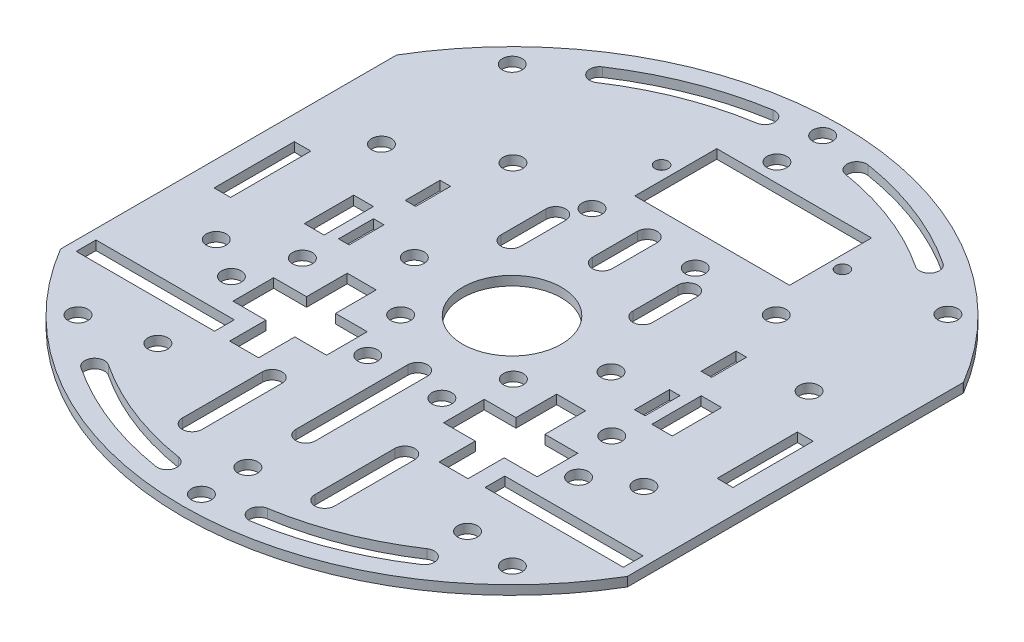
SolidWorks part; units mm, degrees
ref_plane "Plan de face" through (0, 0, 0) normal (0, 0, 1) x (1, 0, 0)
ref_plane "Plan de dessus" through (0, 0, 0) normal (0, 1, 0) x (1, 0, 0)
ref_plane "Plan de droite" through (0, 0, 0) normal (1, 0, 0) x (0, 0, -1)
sketch "Esquisse1" plane through (0, 0, 0) normal (0, 1, 0) x (1, 0, 0)
  line L0 (230, 494) -> (1150, 494) construction
  line L1 (230, 494) -> (1150, 494) construction
  line L2 (1049.7748, 1753.5) -> (2703.7748, 1753.5) construction
  line L3 (35.8344, 116.4831) -> (35.8344, 167.52)
  line L4 (121.9144, 167.4519) -> (121.9144, 116.5513)
  line L5 (88.9323, 158.6153) -> (88.9323, 151.8005) construction
  line L6 (121.9144, 116.5513) -> (121.9144, 116.4831)
  line L7 (55.7773, 128.9032) -> (60.7773, 128.9032)
  line L8 (55.7773, 128.9032) -> (55.7773, 122.7236)
  line L9 (55.7773, 122.7236) -> (60.7773, 122.7236)
  line L10 (60.7773, 122.7236) -> (60.7773, 117.2265)
  line L11 (60.7773, 117.2265) -> (65.1744, 117.2265)
  line L12 (65.1744, 117.2265) -> (65.1744, 122.7236)
  line L13 (65.1744, 122.7236) -> (69.9925, 122.7236)
  line L14 (69.9925, 122.7236) -> (69.9925, 128.9032)
  line L15 (69.9925, 128.9032) -> (65.1744, 128.9032)
  line L16 (65.1744, 128.9032) -> (65.1744, 135.081)
  line L17 (65.1744, 135.081) -> (60.7773, 135.081)
  line L18 (60.7773, 135.081) -> (60.7773, 128.9032)
  line L19 (68.9056, 158.6153) -> (68.9056, 151.8005) construction
  line L20 (70.4056, 158.6153) -> (70.4056, 151.8005)
  line L21 (67.4056, 158.6153) -> (67.4056, 151.8005)
  line L22 (78.7942, 162.6149) -> (78.7942, 155.8001) construction
  line L23 (80.2942, 162.6149) -> (80.2942, 155.8001)
  line L24 (77.2942, 162.6149) -> (77.2942, 155.8001)
  line L25 (68.7987, 115.6611) -> (68.7987, 103.5071) construction
  line L26 (70.2987, 115.6611) -> (70.2987, 103.5071)
  line L27 (67.2987, 115.6611) -> (67.2987, 103.5071)
  line L28 (39.458, 148.3706) -> (41.958, 148.3706)
  line L29 (41.958, 148.3706) -> (41.958, 136.1826)
  line L30 (41.958, 136.1826) -> (39.458, 136.1826)
  line L31 (39.458, 136.1826) -> (39.458, 148.3706)
  line L32 (55.6035, 149.0513) -> (57.2035, 149.0513)
  line L33 (54.0029, 138.3405) -> (51.0029, 138.3405)
  line L34 (54.0029, 138.3405) -> (54.0029, 145.8405)
  line L35 (54.0029, 145.8405) -> (51.0029, 145.8405)
  line L36 (51.0029, 138.3405) -> (51.0029, 145.8405)
  line L37 (55.6035, 138.9387) -> (57.2035, 138.9387)
  line L38 (55.6035, 138.9387) -> (55.6035, 144.2387)
  line L39 (55.6035, 144.2387) -> (57.2035, 144.2387)
  line L40 (57.2035, 138.9387) -> (57.2035, 144.2387)
  line L41 (55.6035, 149.0513) -> (55.6035, 154.3513)
  line L42 (55.6035, 154.3513) -> (57.2035, 154.3513)
  line L43 (57.2035, 149.0513) -> (57.2035, 154.3513)
  line L44 (35.8344, 142.0016) -> (121.9144, 142.0016) construction
  line L45 (78.8744, 142.0016) -> (78.8744, 76.4199) construction
  line L46 (78.9075, 127.6391) -> (78.9075, 110.6391) construction
  line L47 (80.4075, 127.6391) -> (80.4075, 110.6391)
  line L48 (77.4075, 127.6391) -> (77.4075, 110.6391)
  line L49 (35.8344, 162.6149) -> (121.9144, 162.6149) construction
  line L50 (87.4323, 158.6153) -> (87.4323, 151.8005)
  line L51 (90.4323, 158.6153) -> (90.4323, 151.8005)
  line L52 (88.9323, 115.6611) -> (88.9323, 103.5071) construction
  line L53 (87.4323, 115.6611) -> (87.4323, 103.5071)
  line L54 (90.4323, 115.6611) -> (90.4323, 103.5071)
  line L55 (100.5453, 149.0513) -> (100.5453, 154.3513)
  line L56 (102.1454, 154.3551) -> (100.5453, 154.3513)
  line L57 (102.1454, 149.0551) -> (102.1454, 154.3551)
  line L58 (100.5454, 138.9387) -> (100.5454, 144.2387)
  line L59 (102.1454, 144.2387) -> (100.5454, 144.2387)
  line L60 (102.1454, 138.9387) -> (102.1454, 144.2387)
  line L61 (102.1454, 138.9387) -> (100.5454, 138.9387)
  line L62 (106.8661, 138.3405) -> (106.8661, 145.8405)
  line L63 (103.7673, 145.8405) -> (106.8661, 145.8405)
  line L64 (103.7673, 138.3405) -> (103.7673, 145.8405)
  line L65 (103.7673, 138.3405) -> (106.8661, 138.3405)
  line L66 (102.1454, 149.0551) -> (100.5453, 149.0513)
  line L67 (118.245, 136.1826) -> (118.245, 148.3706)
  line L68 (115.8366, 136.1826) -> (118.245, 136.1826)
  line L69 (115.8366, 148.3706) -> (115.8366, 136.1826)
  line L70 (118.245, 148.3706) -> (115.8366, 148.3706)
  line L71 (96.9716, 135.081) -> (96.9716, 128.9032)
  line L72 (92.5745, 135.081) -> (96.9716, 135.081)
  line L73 (92.5745, 128.9032) -> (92.5745, 135.081)
  line L74 (87.7564, 128.9032) -> (92.5745, 128.9032)
  line L75 (87.7564, 122.7236) -> (87.7564, 128.9032)
  line L76 (92.5745, 122.7236) -> (87.7564, 122.7236)
  line L77 (92.5745, 117.2265) -> (92.5745, 122.7236)
  line L78 (96.9716, 117.2265) -> (92.5745, 117.2265)
  line L79 (96.9716, 122.7236) -> (96.9716, 117.2265)
  line L80 (101.9716, 122.7236) -> (96.9716, 122.7236)
  line L81 (101.9716, 128.9032) -> (101.9716, 122.7236)
  line L82 (101.9716, 128.9032) -> (96.9716, 128.9032)
  line L84 (72.4514, 167.0754) -> (95.9525, 167.0754)
  line L85 (72.4514, 167.0754) -> (72.4514, 179.5181)
  line L86 (72.4514, 179.5181) -> (95.9525, 179.5181)
  line L87 (95.9525, 167.0754) -> (95.9525, 179.5181)
  arc A1 (35.8344, 116.4831) -> (121.9144, 116.4831) centre (78.8744, 142.0016) ccw
  circle A2 centre (78.8744, 142.0016) radius 7.5
  arc A3 (121.8796, 167.5788) -> (35.8344, 167.52) centre (78.8744, 142.0016) ccw
  circle A4 centre (55.6386, 111.4684) radius 1.5
  circle A5 centre (52.4216, 125.8435) radius 1.5
  circle A6 centre (46.4093, 129.5605) radius 1.5
  circle A7 centre (45.8266, 109.1504) radius 1.5
  circle A9 centre (55.394, 133.6521) radius 1.5
  circle A10 centre (63.822, 142.2216) radius 1.5
  circle A11 centre (70.318, 133.6521) radius 1.5
  circle A12 centre (73.1582, 125.8134) radius 1.5
  circle A14 centre (78.7794, 94.9342) radius 1.5
  circle A15 centre (58.8593, 162.1633) radius 1.5
  circle A16 centre (78.7794, 101.9917) radius 1.5
  circle A17 centre (45.8266, 175.0806) radius 1.5
  circle A18 centre (78.7794, 182.3243) radius 1.5
  circle A19 centre (46.4093, 154.6416) radius 1.5
  circle A20 centre (78.7794, 189.2658) radius 1.5
  circle A21 centre (70.8644, 162.1633) radius 1.5
  arc A24 (70.4056, 158.6153) -> (67.4056, 158.6153) centre (68.9056, 158.6153) ccw
  arc A25 (67.4056, 151.8005) -> (70.4056, 151.8005) centre (68.9056, 151.8005) ccw
  arc A26 (80.2942, 162.6149) -> (77.2942, 162.6149) centre (78.7942, 162.6149) ccw
  arc A27 (77.2942, 155.8001) -> (80.2942, 155.8001) centre (78.7942, 155.8001) ccw
  arc A30 (70.2987, 115.6611) -> (67.2987, 115.6611) centre (68.7987, 115.6611) ccw
  arc A31 (67.2987, 103.5071) -> (70.2987, 103.5071) centre (68.7987, 103.5071) ccw
  arc A35 (53.8408, 103.6654) -> (71.8854, 96.6187) centre (79.1758, 141.9141) ccw construction
  arc A36 (53.0125, 102.4148) -> (71.647, 95.1377) centre (79.1758, 141.9141) ccw
  arc A37 (54.6692, 104.9159) -> (72.1238, 98.0996) centre (79.1758, 141.9141) ccw
  arc A38 (54.6692, 104.9159) -> (53.0125, 102.4148) centre (53.8408, 103.6654) ccw
  arc A39 (71.647, 95.1377) -> (72.1238, 98.0996) centre (71.8854, 96.6187) ccw
  circle A40 centre (78.9075, 110.6391) radius 1.5
  circle A41 centre (78.9075, 127.6391) radius 1.5
  arc A42 (80.4075, 127.6391) -> (77.4075, 127.6391) centre (78.9075, 127.6391) ccw
  arc A43 (77.4075, 110.6391) -> (80.4075, 110.6391) centre (78.9075, 110.6391) ccw
  arc A44 (53.8408, 180.3378) -> (71.8854, 187.3845) centre (79.1758, 142.0891) cw construction
  arc A45 (53.0125, 181.5883) -> (71.647, 188.8654) centre (79.1758, 142.0891) cw
  arc A46 (54.6692, 179.0872) -> (72.1238, 185.9035) centre (79.1758, 142.0891) cw
  arc A47 (54.6692, 179.0872) -> (53.0125, 181.5883) centre (53.8408, 180.3378) cw
  arc A48 (71.647, 188.8654) -> (72.1238, 185.9035) centre (71.8854, 187.3845) cw
  circle A49 centre (70.4056, 173.1853) radius 1
  arc A50 (87.4323, 158.6153) -> (90.4323, 158.6153) centre (88.9323, 158.6153) cw
  arc A51 (90.4323, 151.8005) -> (87.4323, 151.8005) centre (88.9323, 151.8005) cw
  arc A52 (87.4323, 115.6611) -> (90.4323, 115.6611) centre (88.9323, 115.6611) cw
  arc A53 (90.4323, 103.5071) -> (87.4323, 103.5071) centre (88.9323, 103.5071) cw
  arc A54 (103.908, 103.6654) -> (85.8635, 96.6187) centre (78.573, 141.9141) cw construction
  arc A55 (104.7364, 102.4148) -> (86.1018, 95.1377) centre (78.573, 141.9141) cw
  arc A56 (103.0797, 104.9159) -> (85.6251, 98.0996) centre (78.573, 141.9141) cw
  arc A57 (103.0797, 104.9159) -> (104.7364, 102.4148) centre (103.908, 103.6654) cw
  arc A58 (86.1018, 95.1377) -> (85.6251, 98.0996) centre (85.8635, 96.6187) cw
  arc A59 (103.908, 180.3378) -> (85.8635, 187.3845) centre (78.573, 142.0891) ccw construction
  arc A60 (104.7364, 181.5883) -> (86.1018, 188.8654) centre (78.573, 142.0891) ccw
  arc A61 (103.0797, 179.0872) -> (85.6251, 185.9035) centre (78.573, 142.0891) ccw
  arc A62 (103.0797, 179.0872) -> (104.7364, 181.5883) centre (103.908, 180.3378) ccw
  arc A63 (86.1018, 188.8654) -> (85.6251, 185.9035) centre (85.8635, 187.3845) ccw
  circle A64 centre (97.8643, 173.1853) radius 1
  circle A66 centre (86.5331, 162.1633) radius 1.5
  circle A67 centre (111.3396, 154.6416) radius 1.5
  circle A68 centre (111.7891, 175.2768) radius 1.5
  circle A69 centre (98.8379, 162.1633) radius 1.5
  circle A70 centre (84.4104, 125.8134) radius 1.5
  circle A71 centre (87.3272, 133.7572) radius 1.5
  circle A72 centre (93.7831, 142.1236) radius 1.5
  circle A73 centre (102.2561, 133.7572) radius 1.5
  circle A74 centre (105.1676, 125.8134) radius 1.5
  circle A75 centre (111.8296, 109.1035) radius 1.5
  circle A76 centre (111.3396, 129.5605) radius 1.5
  circle A78 centre (103.8661, 110.2588) radius 1.5
  arc A79 (121.8796, 167.5788) -> (121.9144, 167.4519) centre (121.6662, 167.4519) cw
  point P32 (68.9056, 155.2079)
  point P38 (55.6386, 111.4684)
  point P42 (78.7942, 159.2075)
  point P63 (68.7987, 109.5841)
  point P106 (78.9075, 119.1391)
  point P110 (62.487, 99.1788)
  point P129 (62.487, 184.8244)
  point P138 (35.8344, 167.52)
  point P139 (88.9323, 155.2079)
  point P146 (88.9323, 109.5841)
  point P154 (95.2619, 99.1788)
  point P162 (95.2619, 184.8244)
  point P225 (121.9144, 167.52)
  point P226 (102.1103, 111.4684)
  dimension "D3" = 15
  dimension "D5" = 3
  dimension "D6" = 1.5
  dimension "D7" = 1.5
  dimension "D14" = 3
  dimension "D17" = 2
  dimension "D18" = 3
  dimension "D19" = 3
  dimension "D20" = 3
  dimension "D21" = 3
  dimension "D22" = 3
  dimension "D23" = 3
  dimension "D24" = 3
  dimension "D25" = 3
  dimension "D26" = 3
  dimension "D27" = 3
  dimension "D29" = 3
  dimension "D33" = 1.5
  dimension "D35" = 3
  dimension "D2" = 51.0369
  dimension "D4" = 5
  dimension "D8" = 2.5
  dimension "D9" = 12.1879
  dimension "D10" = 3
  dimension "D11" = 7.5
  dimension "D12" = 1.6
  dimension "D13" = 5.3
  dimension "D15" = 3
  dimension "D16" = 17
  dimension "D28" = 12.1541
  dimension "D30" = 6.8148
  dimension "D31" = 43.04
  dimension "D32" = 43.04
  dimension "D34" = 6.8148
  dimension "D36" = 12.1541
  dimension "D37" = 1.6
  dimension "D38" = 5.3
extrude "Boss.-Extru.1" add sketch "Esquisse1" along normal blind 1.4 contours A79 A3 L3 A1 L6 L4 A76 A74 A72 A70 A68 A66 A55 A58 A56 A57 L54 A53 L53 A52 L51 A51 L50 A50 A45 A48 A46 A47 L57 L66 L55 L56 L60 L61 L58 L59 L33 L36 region at (37.1544, 0, -142.0016)
sketch "Esquisse2" plane through (0, 0, 0) normal (0, -1, 0) x (-1, 0, 0)
  line L0 (-121.9144, 167.4519) -> (-121.9144, 116.4831) construction
  line L1 (-99.4144, 120.3725) -> (-120.4144, 120.3725)
  line L2 (-99.4144, 120.3725) -> (-99.4144, 117.3725)
  line L3 (-99.4144, 117.3725) -> (-120.4144, 117.3725)
  line L4 (-120.4144, 120.3725) -> (-120.4144, 117.3725)
  line L5 (-35.8344, 116.4831) -> (-35.8344, 167.52) construction
  line L6 (-37.3344, 120.3731) -> (-58.3344, 120.3731)
  line L7 (-37.3344, 120.3731) -> (-37.3344, 117.3731)
  line L8 (-37.3344, 117.3731) -> (-58.3344, 117.3731)
  line L9 (-58.3344, 120.3731) -> (-58.3344, 117.3731)
  dimension "D1" = 1.5
  dimension "D2" = 3
  dimension "D3" = 21
  dimension "D4" = 0.8894
  dimension "D5" = 1.5
  dimension "D6" = 0.89
  dimension "D7" = 3
  dimension "D8" = 21
extrude "Enlèv. mat.-Extru.1" cut sketch "Esquisse2" against normal blind 10
